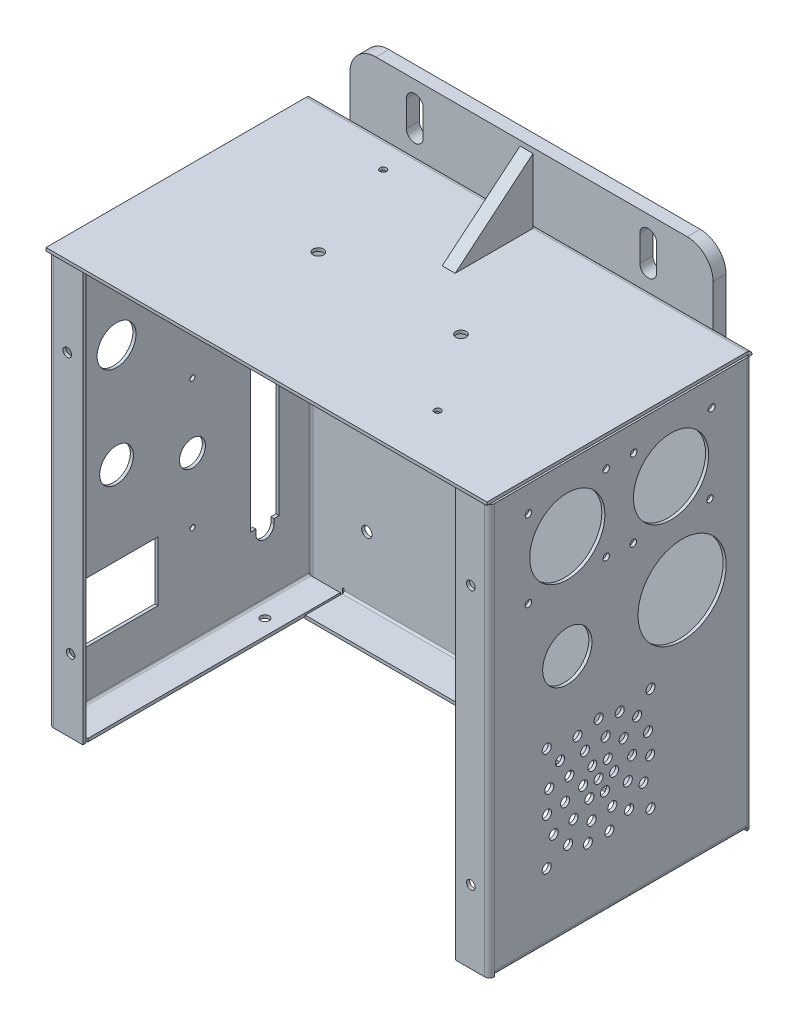
SolidWorks part; units mm, degrees
note: The reader was unsure of these and kept them because the rebuilt part matched: flange length of "边线-法兰1", "边线-法兰2", "边线-法兰3", "边线-法兰4", "边线-法兰5", "边线-法兰6", "边线-法兰7", "边线-法兰8".
ref_plane "前视基准面" through (0, 0, 0) normal (0, 0, 1) x (1, 0, 0)
ref_plane "上视基准面" through (0, 0, 0) normal (0, 1, 0) x (1, 0, 0)
ref_plane "右视基准面" through (0, 0, 0) normal (1, 0, 0) x (0, 0, -1)
sketch "草图1" plane through (0, 0, 0) normal (0, 0, 1) x (1, 0, 0)
  line L1 (-85, 80) -> (85, 80)
  line L2 (-85, 80) -> (-85, -80)
  line L3 (-85, -80) -> (85, -80)
  line L4 (85, 80) -> (85, -80)
  line L5 (-85, 80) -> (85, -80) construction
  line L6 (-85, -80) -> (85, 80) construction
  point P0 (0, 0)
  dimension "D1" = 160
  dimension "D2" = 170
sheet metal parameters "钣金1" thickness 1.2 parameters "D1"=0.7366
base flange "基体-法兰1" sketch "草图1" thickness 1.2 reverse thickness direction no parameters "D1"=0.7366
edge flange "边线-法兰1" sketch "草图5" flange angle 90 flange length 101 flange position material inside bend radius 0.7366 thickness 1.2 relief rectangular parameters "D6"=10
sketch "草图5" plane through (0, 80, 0) normal (0, 1, 0) x (-1, 0, 0)
  line L0 (-85, 0) -> (85, 0) construction
  line L1 (-85, 0) -> (85, 0)
  line L2 (-85, 0) -> (-85, 101)
  line L3 (-85, 101) -> (85, 101)
  line L4 (85, 101) -> (85, 0)
bend "边线折弯1" bend radius 0.7366 bend angle 90 parameters "D5"=1
edge flange "边线-法兰2" sketch "草图8" flange angle 90 flange length 100 flange position material inside bend radius 0.7366 thickness 1.2 relief none parameters "D6"=10
sketch "草图8" plane through (85, 0, 0) normal (1, 0, 0) x (0, 1, 0)
  line L0 (-80, 0) -> (78.0634, 0) construction
  line L1 (-80, 0) -> (78.0634, 0)
  line L2 (-80, 0) -> (-80, 100)
  line L3 (-80, 100) -> (78.0634, 100)
  line L4 (78.0634, 100) -> (78.0634, 0)
bend "边线折弯2" bend radius 0.7366 bend angle 90 parameters "D5"=2
edge flange "边线-法兰3" sketch "草图11" flange angle 90 flange length 100 flange position material inside bend radius 0.7366 thickness 1.2 relief none parameters "D6"=10
sketch "草图11" plane through (-85, 0, 0) normal (-1, 0, 0) x (0, -1, 0)
  line L0 (-78.0634, 0) -> (80, 0) construction
  line L1 (-78.0634, 0) -> (80, 0)
  line L2 (-78.0634, 0) -> (-78.0634, 100)
  line L3 (-78.0634, 100) -> (80, 100)
  line L4 (80, 100) -> (80, 0)
bend "边线折弯3" bend radius 0.7366 bend angle 90 parameters "D5"=3
edge flange "边线-法兰4" sketch "草图15" flange angle 90 flange length 15 flange position material inside bend radius 0.7366 thickness 1.2 relief rectangular parameters "D6"=10
sketch "草图15" plane through (0, -80, 0) normal (0, -1, 0) x (1, 0, 0)
  line L0 (-83.0634, 0) -> (83.0634, 0) construction
  line L1 (-71.0634, 0) -> (71.0634, 0)
  line L3 (-71.0634, 15) -> (71.0634, 15)
  line L5 (71.0634, 15) -> (71.0634, 0)
  line L6 (-71.0634, 0) -> (-71.0634, 15)
bend "边线折弯4" bend radius 0.7366 bend angle 90 parameters "D5"=4
sketch "草图16" plane through (-85, 0, 0) normal (-1, 0, 0) x (0, 0, 1)
  line L0 (100, -80) -> (100, 78.0634) construction
  line L1 (59, -37) -> (88, -37)
  line L2 (59, -37) -> (59, -60)
  line L3 (59, -60) -> (88, -60)
  line L4 (88, -37) -> (88, -60)
  line L5 (59, -37) -> (88, -60) construction
  line L6 (59, -60) -> (88, -37) construction
  line L7 (0.7366, -80) -> (100, -80) construction
  line L10 (0.7366, -80) -> (0.7366, 78.0634) construction
  circle A0 centre (75, -5) radius 6.5
  circle A1 centre (75, 35) radius 7.5
  circle A2 centre (45.7366, -15.6475) radius 5
  circle A3 centre (45.7366, 9.3525) radius 1
  circle A4 centre (45.7366, -40.6475) radius 1
  point P0 (73.5, -48.5)
  dimension "D7" = 13
  dimension "D8" = 15
  dimension "D13" = 10
  dimension "D14" = 2
  dimension "D15" = 2
  dimension "D1" = 23
  dimension "D2" = 29
  dimension "D3" = 12
  dimension "D4" = 20
  dimension "D5" = 75
  dimension "D6" = 40
  dimension "D9" = 25
  dimension "D10" = 25
  dimension "D11" = 50
  dimension "D12" = 25
  dimension "D16" = 45
extrude "切除-拉伸1" cut sketch "草图16" against normal blind 10 normal cut yes
sketch "草图17" plane through (-85, 0, 0) normal (-1, 0, 0) x (0, 0, 1)
  line L0 (0.7366, -80) -> (100, -80) construction
  line L5 (12.3, 5) -> (12.3, -53.25)
  line L6 (23.3, 5) -> (23.3, -53.25)
  line L7 (-1.2, -80) -> (-1.2, 78.0634) construction
  line L8 (23.3, 5) -> (21.3, 5)
  line L9 (23.3, -53.25) -> (21.3, -53.25)
  line L10 (21.3, -55) -> (21.3, -53.25)
  line L11 (14.3, -55) -> (14.3, -53.25)
  line L12 (21.3, 8.5) -> (21.3, 5)
  line L13 (14.3, 8.5) -> (14.3, 5)
  line L15 (14.3, 5) -> (12.3, 5)
  line L18 (14.3, -53.25) -> (12.3, -53.25)
  arc A0 (14.3, -55) -> (21.3, -55) centre (17.8, -55) ccw
  arc A1 (21.3, 8.5) -> (14.3, 8.5) centre (17.8, 8.5) ccw
  dimension "D2" = 7
  dimension "D1" = 63.5
  dimension "D3" = 11
  dimension "D4" = 25
  dimension "D5" = 19
extrude "切除-拉伸2" cut sketch "草图17" against normal blind 10 normal cut yes
sketch "草图18" plane through (0, 0, 0) normal (0, 0, 1) x (1, 0, 0)
  circle A0 centre (-62.3, 5.875) radius 2
  circle A1 centre (-62.3, -54.125) radius 2
  circle A2 centre (27.7, 5.875) radius 2
  circle A3 centre (27.7, -54.125) radius 2
  dimension "D1" = 4
extrude "切除-拉伸3" cut sketch "草图18" against normal blind 10 normal cut yes
sketch "草图19" plane through (0, 78.8, 0) normal (0, -1, 0) x (1, 0, 0)
  circle A0 centre (45, 80) radius 1
  circle A1 centre (-46, 10) radius 1.027
  dimension "D1" = 2
extrude "切除-拉伸4" cut sketch "草图19" against normal blind 10 normal cut yes
sketch "草图20" plane through (0, 78.8, 0) normal (0, -1, 0) x (1, 0, 0)
  circle A1 centre (-31, 50) radius 2
  circle A2 centre (24, 50) radius 2
  dimension "D4" = 4
  dimension "D5" = 4
extrude "切除-拉伸5" cut sketch "草图20" against normal blind 10 normal cut yes
sketch "草图21" plane through (85, 0, 0) normal (1, 0, 0) x (0, 0, -1)
  line L0 (-0.7366, 78.0634) -> (-100, 78.0634) construction
  line L13 (-100, 78.0634) -> (-100, -80) construction
  circle A0 centre (-30, 53.0634) radius 14.5
  circle A1 centre (-70, 53.0634) radius 14.5
  circle A2 centre (-85, 38.0634) radius 0.6607
  circle A3 centre (-85, 68.0634) radius 0.4975
  circle A4 centre (-55, 38.0634) radius 0.5773
  circle A5 centre (-55, 68.0634) radius 0.7707
  circle A6 centre (-45, 38.0634) radius 0.4523
  circle A7 centre (-45, 68.0634) radius 0.6039
  circle A8 centre (-15, 68.0634) radius 0.7557
  circle A9 centre (-15, 38.0634) radius 1
  circle A10 centre (-70, 13.0634) radius 9.5
  dimension "D1" = 29
  dimension "D2" = 29
  dimension "D11" = 2
  dimension "D9" = 19
  dimension "D3" = 30
  dimension "D4" = 30
  dimension "D5" = 30
  dimension "D6" = 30
  dimension "D7" = 25
  dimension "D8" = 30
  dimension "D10" = 25
  dimension "D12" = 10
  dimension "D13" = 40
extrude "切除-拉伸6" cut sketch "草图21" against normal blind 10 normal cut yes
sketch "草图22" plane through (85, 0, 0) normal (1, 0, 0) x (0, 0, -1)
  circle A0 centre (-77.935, -53.8881) radius 1.75
  circle A1 centre (-77.935, -13.8881) radius 1.75
  circle A2 centre (-77.8255, -35.9787) radius 1.75
  circle A3 centre (-76.9562, -27.7078) radius 1.75
  circle A4 centre (-40.6145, -43.8881) radius 1.75
  circle A5 centre (-46.1793, -50.0684) radius 1.75
  circle A6 centre (-53.7768, -53.451) radius 1.75
  circle A7 centre (-62.0933, -53.451) radius 1.75
  circle A8 centre (-69.6907, -50.0684) radius 1.75
  circle A9 centre (-75.2555, -43.8881) radius 1.75
  circle A10 centre (-52.6475, -45.7642) radius 1.75
  circle A11 centre (-60.6379, -46.604) radius 1.75
  circle A12 centre (-67.5959, -42.5868) radius 1.75
  circle A13 centre (-37.935, -53.8881) radius 1.75
  circle A14 centre (-57.935, -33.8881) radius 1.75
  circle A15 centre (-57.935, -13.8881) radius 1.75
  circle A16 centre (-49.8003, -15.6172) radius 1.75
  circle A17 centre (-72.7979, -20.5055) radius 1.75
  circle A18 centre (-66.0698, -15.6172) radius 1.75
  circle A19 centre (-48.2742, -25.1894) radius 1.75
  circle A20 centre (-46.6767, -40.3881) radius 1.75
  circle A21 centre (-70.8638, -35.247) radius 1.75
  circle A22 centre (-69.1934, -27.3881) radius 1.75
  circle A23 centre (-63.2226, -22.012) radius 1.75
  circle A24 centre (-55.2322, -21.1722) radius 1.75
  circle A25 centre (-60.3755, -28.4068) radius 1.75
  circle A26 centre (-54.4083, -29.034) radius 1.75
  circle A27 centre (-51.9679, -34.5153) radius 1.75
  circle A28 centre (-55.4946, -39.3694) radius 1.75
  circle A29 centre (-61.4618, -38.7422) radius 1.75
  circle A30 centre (-63.9022, -33.2609) radius 1.75
  circle A31 centre (-37.935, -13.8881) radius 1.75
  circle A32 centre (-43.0721, -20.5055) radius 1.75
  circle A33 centre (-38.9139, -27.7078) radius 1.75
  circle A34 centre (-38.0446, -35.9787) radius 1.75
  circle A35 centre (-45.0063, -32.5292) radius 1.75
extrude "切除-拉伸7" cut sketch "草图22" against normal blind 10 normal cut yes
sketch "草图23" plane through (85, 0, 0) normal (1, 0, 0) x (0, 0, -1)
  line L0 (-0.7366, 78.0634) -> (-0.7366, -80) construction
  line L1 (-101, 80) -> (-0.7366, 80) construction
  circle A0 centre (-25.7366, 13) radius 17
  dimension "D3" = 34
  dimension "D1" = 25
  dimension "D2" = 67
extrude "切除-拉伸8" cut sketch "草图23" against normal blind 10 normal cut yes
edge flange "边线-法兰5" sketch "草图26" flange angle 90 flange length 12 flange position material inside bend radius 0.7366 thickness 1.2 relief rectangular parameters "D6"=10
bend "边线折弯10" bend radius 0.7366 bend angle 90 parameters "D5"=0
bend "边线折弯11" bend radius 0.7366 bend angle 90 parameters "D5"=0
bend "边线折弯13" bend radius 0.7366 bend angle 90 parameters "D5"=0
sketch "草图26" plane through (-83.8, 0, 100) normal (0, 0, 1) x (0, -1, 0)
  line L2 (-78.0634, 0) -> (-78.0634, 12)
  line L3 (-78.0634, 12) -> (80, 12)
  line L4 (80, 12) -> (80, 0)
  line L5 (80, 0) -> (-78.0634, 0) construction
  line L6 (80, 0) -> (-78.0634, 0)
bend "边线折弯14" bend radius 0.7366 bend angle 90 parameters "D5"=0
bend "边线折弯16" bend radius 0.7366 bend angle 90 parameters "D5"=0
bend "边线折弯18" bend radius 0.7366 bend angle 90 parameters "D5"=9
edge flange "边线-法兰6" sketch "草图29" flange angle 90 flange length 12 flange position material inside bend radius 0.7366 thickness 1.2 relief rectangular parameters "D6"=10
sketch "草图29" plane through (83.8, 0, 100) normal (0, 0, 1) x (0, 1, 0)
  line L0 (78.0634, 0) -> (-80, 0) construction
  line L1 (78.0634, 0) -> (-80, 0)
  line L2 (-80, 0) -> (-80, 12)
  line L3 (-80, 12) -> (78.0634, 12)
  line L4 (78.0634, 12) -> (78.0634, 0)
bend "边线折弯15" bend radius 0.7366 bend angle 90 parameters "D5"=0
bend "边线折弯17" bend radius 0.7366 bend angle 90 parameters "D5"=0
bend "边线折弯19" bend radius 0.7366 bend angle 90 parameters "D5"=10
edge flange "边线-法兰7" sketch "草图32" flange angle 90 flange length 12 flange position material inside bend radius 0.7366 thickness 1.2 relief none parameters "D6"=10
sketch "草图32" plane through (83.8, -80, 0) normal (0, -1, 0) x (0, 0, 1)
  line L2 (0.7366, 0) -> (0.7366, 12)
  line L3 (0.7366, 12) -> (98.0634, 12)
  line L4 (98.0634, 12) -> (98.0634, 0)
  line L5 (98.0634, 0) -> (0.7366, 0) construction
  line L6 (98.0634, 0) -> (0.7366, 0)
bend "边线折弯7" bend radius 0.7366 bend angle 90 parameters "D5"=7
edge flange "边线-法兰8" sketch "草图35" flange angle 90 flange length 12 flange position material inside bend radius 0.7366 thickness 1.2 relief none parameters "D6"=10
sketch "草图35" plane through (-83.8, -80, 0) normal (0, -1, 0) x (0, 0, -1)
  line L0 (-0.7366, 0) -> (-98.0634, 0) construction
  line L1 (-0.7366, 0) -> (-98.0634, 0)
  line L2 (-98.0634, 0) -> (-98.0634, 12)
  line L3 (-98.0634, 12) -> (-0.7366, 12)
  line L4 (-0.7366, 12) -> (-0.7366, 0)
bend "边线折弯8" bend radius 0.7366 bend angle 90 parameters "D5"=8
hole_wizard "M3 螺纹孔1" positions "草图37" profile "草图36" tap size "M3" standard "ISO"
sketch "草图37" plane through (85, 0, 0) normal (1, 0, 0) x (0, 0, -1)
  circle A0 centre (-55, 38.0634) radius 0.5773 construction
  circle A1 centre (-45, 68.0634) radius 0.6039 construction
  circle A2 centre (-45, 38.0634) radius 0.4523 construction
  circle A3 centre (-15, 68.0634) radius 0.7557 construction
  point P1 (-85, 38.0634)
  point P4 (-85, 68.0634)
  point P7 (-55, 68.0634)
  point P10 (-55, 38.6407)
  point P14 (-44.3961, 68.0634)
  point P18 (-44.5477, 38.0634)
  point P22 (-14.2443, 68.0634)
  point P26 (-15, 38.0634)
sketch "草图36" plane through (85, 38.0634, 85) normal (0, 1, 0) x (0, 0, -1)
  line L0 (0, 0) -> (0, 8.2511)
  line L1 (0, 8.2511) -> (1.25, 7.5)
  line L2 (1.25, 7.5) -> (1.25, 0)
  line L5 (1.25, 0) -> (0, 0)
  line L10 (0, 8.2511) -> (-1.25, 7.5) construction
  line L11 (0, -6.35) -> (0, 107.95) construction
  dimension "螺纹孔钻头直径" = 2.5
  dimension "螺纹孔钻头深度" = 7.5
  dimension "导头角度" = 118
cosmetic thread "孔螺蚊线1" parameters "D1"=1.2, "D2"=3
cosmetic thread "孔螺蚊线2" parameters "D1"=1.2, "D2"=3
cosmetic thread "孔螺蚊线3" parameters "D1"=1.2, "D2"=3
cosmetic thread "孔螺蚊线4" parameters "D1"=1.2, "D2"=3
cosmetic thread "孔螺蚊线5" parameters "D1"=1.2, "D2"=3
cosmetic thread "孔螺蚊线6" parameters "D1"=1.2, "D2"=3
cosmetic thread "孔螺蚊线7" parameters "D1"=1.2, "D2"=3
cosmetic thread "孔螺蚊线8" parameters "D1"=1.2, "D2"=3
hole_wizard "M3 螺纹孔2" positions "草图39" profile "草图38" tap size "M3" standard "ISO"
sketch "草图39" plane through (0, 80, 0) normal (0, 1, 0) x (-1, 0, 0)
  point P13 (-45, 80)
  point P19 (46, 10)
sketch "草图38" plane through (45, 80, 80) normal (1, 0, 0) x (0, 0, 1)
  line L0 (0, 0) -> (0, 8.2511)
  line L1 (0, 8.2511) -> (1.25, 7.5)
  line L2 (1.25, 7.5) -> (1.25, 0)
  line L5 (1.25, 0) -> (0, 0)
  line L10 (0, 8.2511) -> (-1.25, 7.5) construction
  line L11 (0, -6.35) -> (0, 107.95) construction
  dimension "螺纹孔钻头直径" = 2.5
  dimension "螺纹孔钻头深度" = 7.5
  dimension "导头角度" = 118
cosmetic thread "孔螺蚊线9" parameters "D1"=1.2, "D2"=3
cosmetic thread "孔螺蚊线11" parameters "D1"=1.2, "D2"=3
hole_wizard "M4 螺纹孔1" positions "草图41" profile "草图40" tap size "M4" standard "ISO"
sketch "草图41" plane through (0, 0, 100) normal (0, 0, 1) x (1, 0, 0)
  line L0 (-71.8, -80) -> (-71.8, 78.0634) construction
  line L1 (-71.8, 78.0634) -> (-83.0634, 78.0634) construction
  line L2 (71.8, 78.0634) -> (71.8, -80) construction
  point P0 (77.8, 48.0634)
  point P1 (-77.8, 48.0634)
  point P4 (-76.5235, -51.9366)
  point P6 (77.8, -51.9366)
  dimension "D1" = 6
  dimension "D2" = 30
  dimension "D3" = 100
  dimension "D4" = 6
sketch "草图40" plane through (77.8, 48.0634, 100) normal (1, 0, 0) x (0, -1, 0)
  line L0 (0, 0) -> (0, 11.0914)
  line L1 (0, 11.0914) -> (1.65, 10.1)
  line L2 (1.65, 10.1) -> (1.65, 0)
  line L5 (1.65, 0) -> (0, 0)
  line L10 (0, 11.0914) -> (-1.65, 10.1) construction
  line L11 (0, -6.35) -> (0, 107.95) construction
  dimension "螺纹孔钻头直径" = 3.3
  dimension "螺纹孔钻头深度" = 10.1
  dimension "导头角度" = 118
cosmetic thread "孔螺蚊线12" parameters "D1"=1.2, "D2"=4
cosmetic thread "孔螺蚊线13" parameters "D1"=1.2, "D2"=4
cosmetic thread "孔螺蚊线14" parameters "D1"=1.2, "D2"=4
cosmetic thread "孔螺蚊线15" parameters "D1"=1.2, "D2"=4
sketch "草图42" plane through (0, 0, -1.2) normal (0, 0, -1) x (-1, 0, 0)
  line L0 (85, 80) -> (-85, 80) construction
  line L1 (70, 105) -> (-70, 105)
  line L2 (70, 105) -> (70, 55)
  line L3 (70, 55) -> (-70, 55)
  line L4 (-70, 105) -> (-70, 55)
  line L5 (70, 105) -> (-70, 55) construction
  line L6 (70, 55) -> (-70, 105) construction
  line L7 (0, 78.0634) -> (0, 172.9953) construction
  line L8 (83.0634, 78.0634) -> (-83.0634, 78.0634) construction
  point P0 (0, 80)
  dimension "D1" = 25
  dimension "D2" = 50
  dimension "D3" = 140
  dimension "D4" = 0
extrude "凸台-拉伸1" add sketch "草图42" along normal blind 5 separate body
fillet "圆角1" radius 10 2 edges at (-70, 105, -3.7) (70, 105, -3.7)
sketch "草图43" plane through (0, 0, 0) normal (1, 0, 0) x (0, 0, -1)
  line L0 (-101, 80) -> (-0.7366, 80) construction
  line L1 (-30.7366, 80) -> (-0.7366, 80)
  line L2 (-0.7366, 80) -> (-0.7366, 105)
  line L3 (-0.7366, 105) -> (-30.7366, 80)
  dimension "D1" = 30
  dimension "D2" = 25
extrude "凸台-拉伸2" add sketch "草图43" along normal mid plane 5 separate body
sketch "草图44" plane through (0, 0, -1.2) normal (0, 0, 1) x (1, 0, 0)
  line L0 (-45, 87) -> (-45, 97) construction
  line L1 (-48.25, 87) -> (-48.25, 97)
  line L2 (-41.75, 87) -> (-41.75, 97)
  line L3 (-70, 55) -> (-70, 95) construction
  line L4 (-60, 105) -> (60, 105) construction
  arc A0 (-48.25, 87) -> (-41.75, 87) centre (-45, 87) ccw
  arc A1 (-41.75, 97) -> (-48.25, 97) centre (-45, 97) ccw
  point P2 (-45, 92)
  dimension "D1" = 6.5
  dimension "D2" = 25
  dimension "D3" = 8
  dimension "D4" = 10
extrude "切除-拉伸9" cut sketch "草图44" against normal blind 5 normal cut yes
mirror "镜向1" about plane through (0, 0, 0) normal (1, 0, 0) of "切除-拉伸9"
hole_wizard "M4 螺纹孔2" positions "草图46" profile "草图45" tap size "M4" standard "ISO"
sketch "草图46" plane through (0, -80, 0) normal (0, -1, 0) x (1, 0, 0)
  line L0 (-71.8, 0.7366) -> (-71.8, 98.0634) construction
  line L1 (70, -1.2) -> (-70, -1.2) construction
  line L2 (71.8, 98.0634) -> (71.8, 0.7366) construction
  point P0 (-77.8, 23.8)
  point P1 (77.8, 23.8)
  dimension "D1" = 6
  dimension "D2" = 25
  dimension "D3" = 6
sketch "草图45" plane through (-77.8, -80, 23.8) normal (1, 0, 0) x (0, 0, -1)
  line L0 (0, 0) -> (0, 11.0914)
  line L1 (0, 11.0914) -> (1.65, 10.1)
  line L2 (1.65, 10.1) -> (1.65, 0)
  line L5 (1.65, 0) -> (0, 0)
  line L10 (0, 11.0914) -> (-1.65, 10.1) construction
  line L11 (0, -6.35) -> (0, 107.95) construction
  dimension "螺纹孔钻头直径" = 3.3
  dimension "螺纹孔钻头深度" = 10.1
  dimension "导头角度" = 118
cosmetic thread "孔螺蚊线16" parameters "D1"=1.2, "D2"=4
cosmetic thread "孔螺蚊线17" parameters "D1"=1.2, "D2"=4
flat pattern "平板型式1" [suppressed]
sketch "折弯-线1" plane through (0, 0, 0) normal (0, 1, 0) x (-1, 0, 0)
bend of the flat pattern "展开-<边线折弯1>1"
bend of the flat pattern "展开-<边线折弯2>1"
bend of the flat pattern "展开-<边线折弯3>1"
bend of the flat pattern "展开-<边线折弯4>1"
bend of the flat pattern "展开-<边线折弯7>1"
bend of the flat pattern "展开-<边线折弯8>1"
bend of the flat pattern "展开-<边线折弯18>1"
bend of the flat pattern "展开-<边线折弯19>1"
